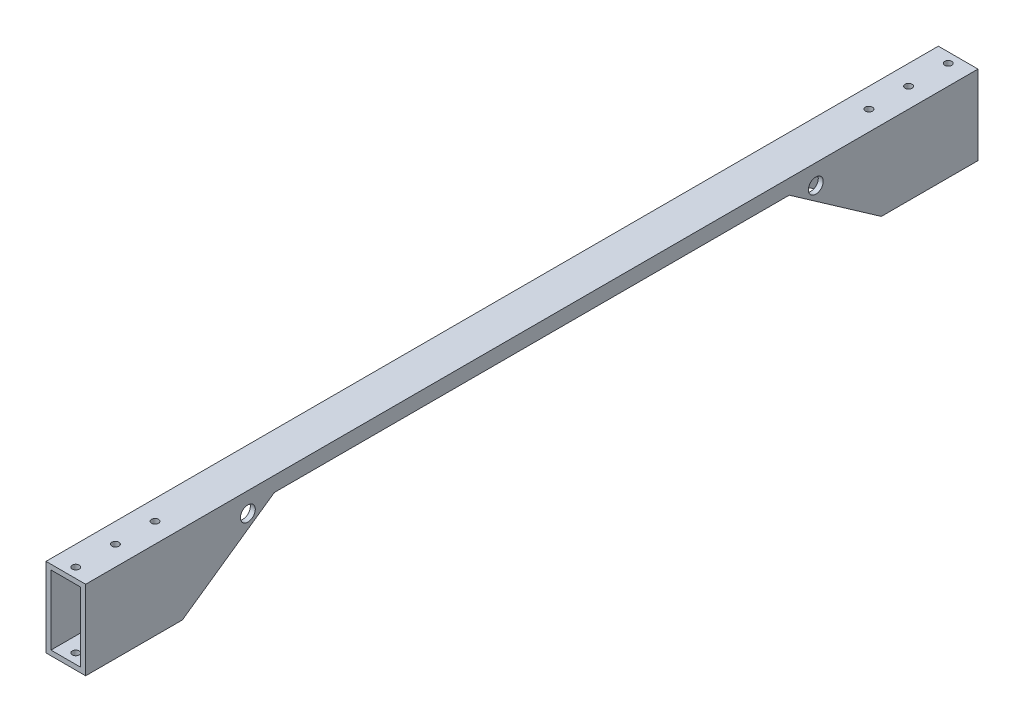
SolidWorks part; units mm, degrees
material "6061-T6 (SS)"
ref_plane "Front Plane" through (0, 0, 0) normal (0, 0, 1) x (1, 0, 0)
ref_plane "Top Plane" through (0, 0, 0) normal (0, 1, 0) x (1, 0, 0)
ref_plane "Right Plane" through (0, 0, 0) normal (1, 0, 0) x (0, 0, -1)
sketch "Sketch1" plane through (0, 0, 0) normal (0, 0, 1) x (1, 0, 0)
  line L1 (-12.7, -25.4) -> (12.7, -25.4)
  line L2 (-12.7, -25.4) -> (-12.7, 25.4)
  line L3 (-12.7, 25.4) -> (12.7, 25.4)
  line L4 (12.7, -25.4) -> (12.7, 25.4)
  line L5 (-12.7, -25.4) -> (12.7, 25.4) construction
  line L6 (-12.7, 25.4) -> (12.7, -25.4) construction
  point P0 (0, 0)
  dimension "D1" = 50.8
  dimension "D2" = 25.4
extrude "Extrude-Thin1" add sketch "Sketch1" along normal blind 571.5 thin thin type one direction reverse wall 3.175
hole_wizard "#8 Clearance Hole1" positions "3DSketch1" profile "Sketch3" hole size "#8" standard "ANSI Inch" end condition through all
sketch3d "3DSketch1"
  line L1 (12.7, 25.4, 0) -> (-12.7, 25.4, 0) construction
  line L6 (0, 25.4, 571.5) -> (0, 25.4, 0) construction
  line L7 (12.7, 25.4, 571.5) -> (-12.7, 25.4, 571.5) construction
  point P57 (0, 25.4, 6.35)
  point P59 (0, 25.4, 31.75)
  point P61 (0, 25.4, 57.15)
  point P63 (0, 25.4, 539.75)
  point P65 (0, 25.4, 514.35)
  point P67 (0, 25.4, 565.15)
  dimension "D1" = 25.4
  dimension "D2" = 25.4
  dimension "D3" = 6.35
  dimension "D4" = 25.4
  dimension "D5" = 25.4
  dimension "D6" = 6.35
sketch "Sketch3" plane through (0, 25.4, 565.15) normal (1, 0, 0) x (0, 0, 1)
  line L0 (0, 0) -> (0, 50.8)
  line L1 (0, 50.8) -> (2.2479, 50.8)
  line L2 (2.2479, 50.8) -> (2.2479, 0)
  line L5 (2.2479, 0) -> (0, 0)
  line L11 (0, -6.35) -> (0, 107.95) construction
  dimension "Thru Hole Dia." = 4.4958
  dimension "Thru Hole Depth" = 50.8
sketch "Sketch10" plane through (12.7, 0, 0) normal (1, 0, 0) x (0, 0, -1)
  line L0 (-509.5875, -25.4) -> (-450.6407, 15.875)
  line L2 (-571.5, -25.4) -> (0, -25.4) construction
  line L3 (-450.6407, 15.875) -> (-120.8593, 15.875)
  line L4 (-120.8593, 15.875) -> (-61.9125, -25.4)
  line L5 (-285.75, -25.4) -> (-285.75, 15.875) construction
  line L6 (-509.5875, -25.4) -> (-61.9125, -25.4)
  point P6 (-81.9233, 15.875)
  point P9 (-474.4898, 15.875)
  point P10 (-491.3529, -25.4)
  dimension "D1" = 447.675
  dimension "D2" = 41.275
  dimension "D3" = 35
extrude "Cut-Extrude1" cut sketch "Sketch10" against normal through all
hole_wizard "3/8 (0.375) Diameter Hole1" positions "Sketch11" profile "Sketch12" hole size "3/8" standard "ANSI Inch" end condition through all
sketch "Sketch11" plane through (-12.7, -44.45, 285.75) normal (1, 0, 0) x (0, 0, -1)
  point P0 (-181.864, 86.995)
  point P3 (-169.164, 78.74)
  point P6 (169.164, 78.74)
  point P9 (181.864, 86.995)
  point P12 (181.864, 57.15)
  point P15 (-181.864, 57.15)
sketch "Sketch12" plane through (-12.7, 42.545, 467.614) normal (0, 1, 0) x (0, 0, 1)
  line L0 (0, 0) -> (0, 25.4)
  line L1 (0, 25.4) -> (4.7625, 25.4)
  line L2 (4.7625, 25.4) -> (4.7625, 0)
  line L3 (4.7625, 0) -> (0, 0)
  line L4 (0, -6.35) -> (0, 107.95) construction
  dimension "Thru Hole Dia." = 9.525
  dimension "Thru Hole Depth" = 25.4
